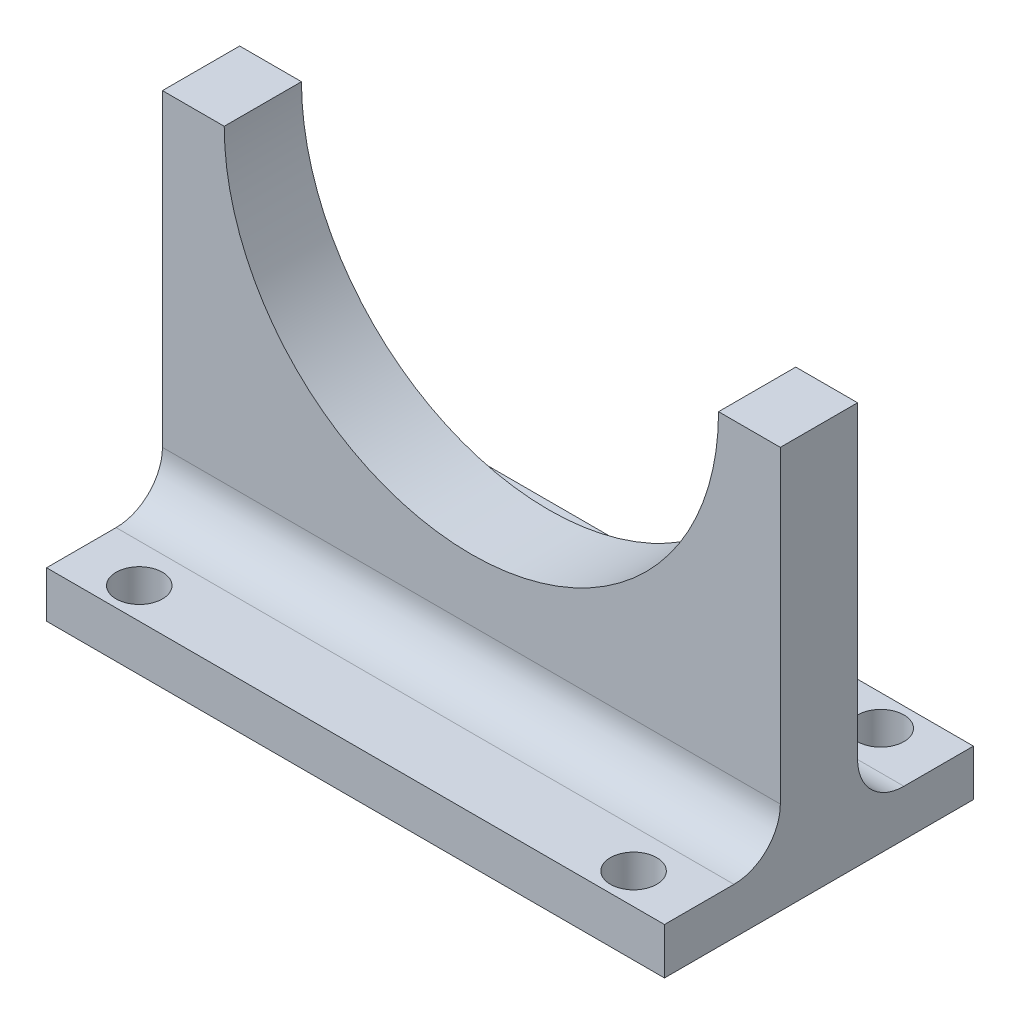
SolidWorks part; units mm, degrees
ref_plane "Front Plane" through (0, 0, 0) normal (0, 0, 1) x (1, 0, 0)
ref_plane "Top Plane" through (0, 0, 0) normal (0, 1, 0) x (1, 0, 0)
ref_plane "Right Plane" through (0, 0, 0) normal (1, 0, 0) x (0, 0, -1)
sketch "Sketch1" plane through (0, 0, 0) normal (0, 0, 1) x (1, 0, 0)
  line L1 (-20, 13) -> (20, 13)
  line L2 (-20, 13) -> (-20, -13)
  line L3 (-20, -13) -> (20, -13)
  line L4 (20, 13) -> (20, -13)
  line L5 (-20, 13) -> (20, -13) construction
  line L6 (-20, -13) -> (20, 13) construction
  point P0 (0, 0)
  dimension "D1" = 40
  dimension "D2" = 26
extrude "Boss-Extrude1" add sketch "Sketch1" along normal blind 2.5 and the other way blind 2.5
sketch "Sketch2" plane through (0, 0, -2.5) normal (0, 0, -1) x (-1, 0, 0)
  line L0 (0, 0) -> (0, 20.0685) construction
  line L1 (-20, 13) -> (20, 13) construction
  circle A0 centre (0, 13) radius 16
  dimension "D1" = 32
extrude "Cut-Extrude1" cut sketch "Sketch2" against normal through all
sketch "Sketch3" plane through (0, 0, 0) normal (0, 0, 1) x (1, 0, 0)
  line L0 (-20, 13) -> (-20, -13) construction
  line L1 (-20, -10) -> (20, -10)
  line L2 (-20, -10) -> (-20, -13)
  line L3 (-20, -13) -> (20, -13)
  line L4 (20, -10) -> (20, -13)
  dimension "D1" = 3
extrude "Boss-Extrude2" add sketch "Sketch3" along normal blind 10 and the other way blind 10
fillet "Fillet1" radius 3 2 edges at (0, -10, -2.5) (0, -10, 2.5)
sketch "Sketch4" plane through (0, -10, 0) normal (0, 1, 0) x (1, 0, 0)
  line L0 (20, 10) -> (20, 5.5) construction
  line L1 (20, 10) -> (-20, 10) construction
  circle A0 centre (16, 8) radius 1.5
  dimension "D1" = 3
  dimension "D2" = 4
  dimension "D3" = 2
extrude "Cut-Extrude2" cut sketch "Sketch4" against normal through all
mirror "Mirror1" about plane through (0, 0, 0) normal (0, 0, 1) of "Cut-Extrude2"
mirror "Mirror2" about plane through (0, 0, 0) normal (1, 0, 0) of "Mirror1", "Cut-Extrude2"
